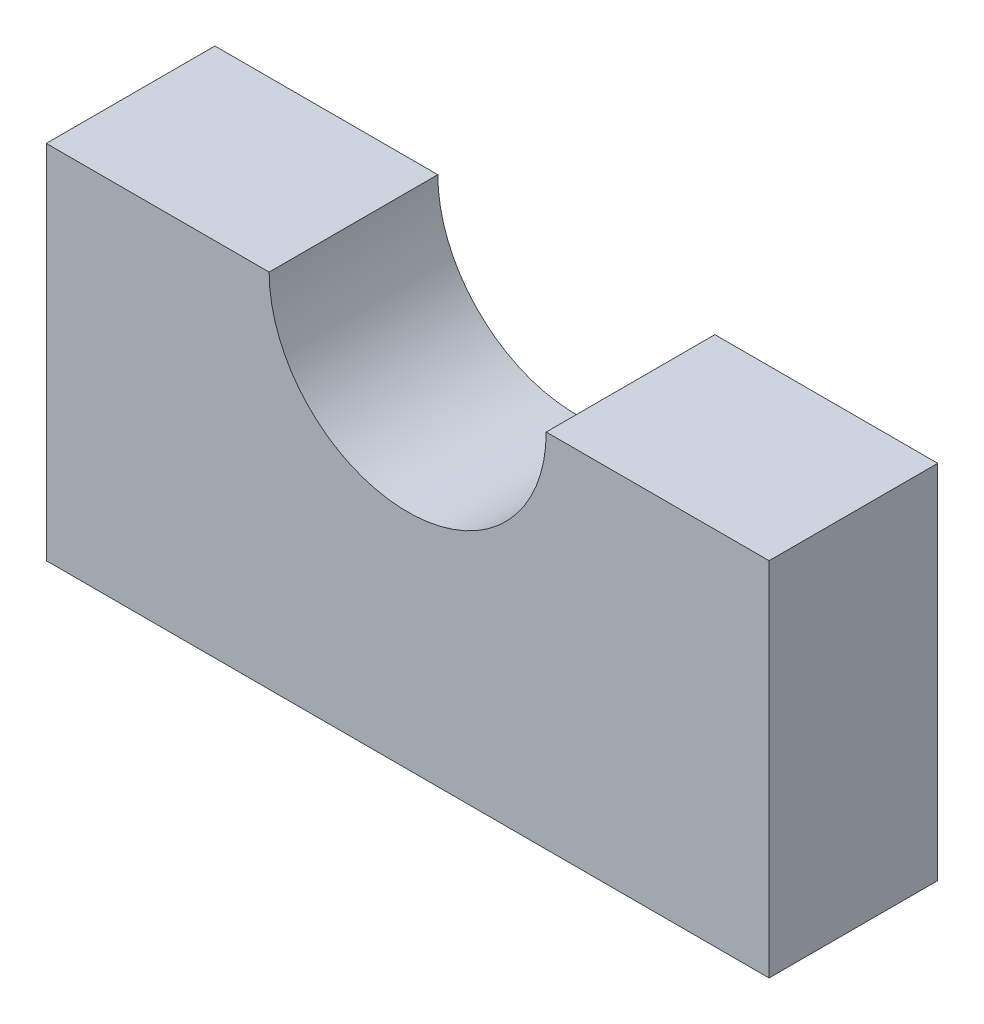
SolidWorks part; units mm, degrees
ref_plane "Front Plane" through (0, 0, 0) normal (0, 0, 1) x (1, 0, 0)
ref_plane "Top Plane" through (0, 0, 0) normal (0, 1, 0) x (1, 0, 0)
ref_plane "Right Plane" through (0, 0, 0) normal (1, 0, 0) x (0, 0, -1)
sketch "Sketch1" plane through (0, 0, 0) normal (0, 0, 1) x (1, 0, 0)
  line L1 (-38.1, -38.1) -> (38.1, -38.1)
  line L3 (-14.605, 0) -> (-38.1, 0)
  line L4 (14.605, 0) -> (38.1, 0)
  line L5 (38.1, 0) -> (38.1, -38.1)
  line L6 (-38.1, 0) -> (-38.1, -38.1)
  line L7 (0, -38.1) -> (0, 0) construction
  circle A0 centre (0, 0) radius 14.605 construction
  arc A1 (-14.605, 0) -> (14.605, 0) centre (0, 0) ccw
  point P5 (0, -0.4381)
  dimension "D1" = 29.21
  dimension "D3" = 76.2
  dimension "D2" = 38.1
extrude "Boss-Extrude1" add sketch "Sketch1" along normal blind 17.78 contours A1 L1 region at (0, -20.7267, 0)
